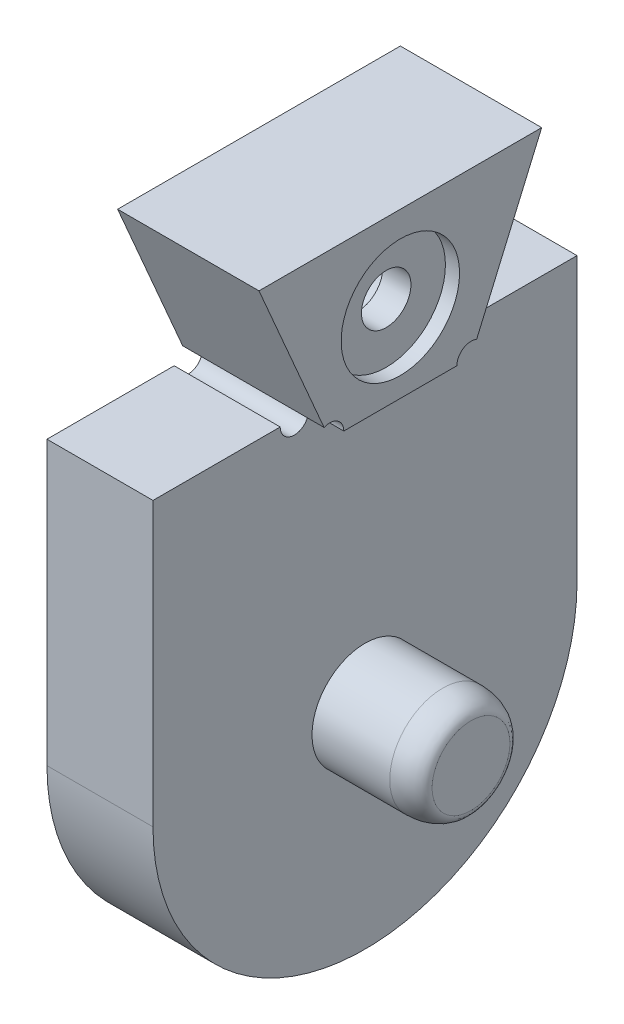
SolidWorks part; units mm, degrees
other "Markup1"
sketch "Sketch42" plane through (-7.99, -35.0001, 20.95) normal (0.6581, -0.0086, 0.7529) x (0.7529, -0.0016, -0.6581)
ref_plane "Front Plane" through (0, 0, 0) normal (0, 0, 1) x (1, 0, 0)
ref_plane "Top Plane" through (0, 0, 0) normal (0, 1, 0) x (1, 0, 0)
ref_plane "Right Plane" through (0, 0, 0) normal (1, 0, 0) x (0, 0, -1)
sketch "Sketch2" plane through (0, 0, 0) normal (0, 0, 1) x (1, 0, 0)
  line L0 (-7.65, 18.1811) -> (-7.65, 14.59)
  line L1 (-7.65, 14.59) -> (7.65, 14.59)
  line L2 (7.65, 14.59) -> (7.65, 18.1811)
  line L3 (7.65, 18.1811) -> (9.45, 18.1811)
  line L4 (9.45, 18.1811) -> (9.45, 21.2003)
  line L5 (-7.65, 18.1811) -> (-9.45, 18.1811)
  line L6 (-9.45, 18.1811) -> (-9.45, 21.2003)
  line L7 (-14.7095, 40) -> (-23, 40)
  line L8 (-23, 40) -> (-23, 0)
  line L10 (14.7095, 40) -> (23, 40)
  line L11 (23, 40) -> (23, 0)
  line L13 (-23, 0) -> (23, 0)
  arc A0 (14.7095, 40) -> (-14.7095, 40) centre (0, 40) ccw
  arc A4 (9.45, 21.2003) -> (-9.45, 21.2003) centre (0, 31.9993) ccw
  point P6 (0, 14.59)
  point P15 (0, 0)
  dimension "D1" = 8.2905
  dimension "D12" = 3.5911
  dimension "D16" = 14.35
  dimension "D17" = 14.7095
  dimension "D2" = 8.2905
  dimension "D3" = 25.41
  dimension "D4" = 40
  dimension "D5" = 0
  dimension "D6" = 0
  dimension "D7" = 46
  dimension "D9" = 3.0191
  dimension "D10" = 1.8
  dimension "D11" = 1.8
  dimension "D13" = 15.3
  dimension "D14" = 3.0191
  dimension "D15" = 3.5911
extrude "Boss-Extrude1" add sketch "Sketch2" along normal blind 20.95
sketch "Sketch3" plane through (0, 0, 0) normal (0, 0, 1) x (1, 0, 0)
  line L7 (-14.7095, 40) -> (-23, 40)
  line L8 (-23, 40) -> (-23, 0)
  line L9 (14.7095, 40) -> (23, 40)
  line L10 (23, 40) -> (23, 0)
  line L11 (-23, 0) -> (23, 0)
  line L12 (23, 40) -> (14.7095, 40) construction
  line L13 (-23, 40) -> (-23, 0) construction
  line L17 (-23, 0) -> (23, 0) construction
  line L19 (23, 0) -> (23, 40) construction
  arc A0 (14.7095, 40) -> (-14.7095, 40) centre (0, 40) ccw
  arc A1 (14.7095, 40) -> (-14.7095, 40) centre (0, 40) ccw construction
  dimension "D1" = 0
extrude "Boss-Extrude2" add sketch "Sketch3" against normal blind 9.05
sketch "Sketch6" plane through (0, 0, 20.95) normal (0, 0, 1) x (1, 0, 0)
  line L0 (-14.7095, 40) -> (-23, 40) construction
  line L1 (-23, 40) -> (-23, 0) construction
  line L2 (23, 40) -> (14.7095, 40) construction
  line L3 (23, 0) -> (23, 40) construction
  circle A0 centre (-17.5, 32) radius 2
  circle A1 centre (17.5, 32) radius 2
  dimension "D1" = 8
  dimension "D2" = 5.5
  dimension "D3" = 4
  dimension "D4" = 8
  dimension "D5" = 5.5
  dimension "D6" = 4
extrude "Cut-Extrude2" cut sketch "Sketch6" against normal blind 10
sketch "Sketch7" plane through (0, 0, 20.95) normal (0, 0, 1) x (1, 0, 0)
  line L0 (-17.5, 32) -> (17.5, 32) construction
  line L3 (-17.5, 35.75) -> (17.5, 35.75)
  line L4 (-17.5, 28.25) -> (17.5, 28.25)
  arc A2 (-17.5, 35.75) -> (-17.5, 28.25) centre (-17.5, 32) ccw
  arc A3 (17.5, 28.25) -> (17.5, 35.75) centre (17.5, 32) ccw
  circle A4 centre (-17.5, 32) radius 2 construction
  circle A5 centre (-17.5, 32) radius 2 construction
  circle A6 centre (17.5, 32) radius 2 construction
  point P2 (0, 32)
  dimension "D2" = 7.5
  dimension "D3" = 1.75
  dimension "D4" = 1.75
  dimension "D1" = 3.75
extrude "Cut-Extrude3" cut sketch "Sketch7" against normal blind 2.75
sketch "Sketch8" plane through (0, 0, 20.95) normal (0, 0, 1) x (1, 0, 0)
  line L0 (-14.7095, 40) -> (-23, 40) construction
  line L1 (-14.7095, 40) -> (-23, 40)
  line L2 (-14.7095, 40) -> (-14.7095, 36.75)
  line L3 (-14.7095, 36.75) -> (-23, 36.75)
  line L4 (-23, 40) -> (-23, 36.75)
  line L5 (14.7095, 40) -> (23, 40)
  line L6 (14.7095, 40) -> (14.7095, 36.75)
  line L7 (14.7095, 36.75) -> (23, 36.75)
  line L8 (23, 40) -> (23, 36.75)
  line L9 (-23, 40) -> (-23, 0) construction
  line L10 (-13.8512, 35.75) -> (-17.5, 35.75) construction
  line L11 (17.5, 35.75) -> (13.8512, 35.75) construction
  line L12 (23, 0) -> (23, 40) construction
  line L13 (23, 40) -> (14.7095, 40) construction
  dimension "D2" = 1
  dimension "D3" = 1
extrude "Cut-Extrude4" cut sketch "Sketch8" along normal through all both and the other way through all
sketch "Sketch11" plane through (0, 0, -9.05) normal (0, 0, -1) x (-1, 0, 0)
  circle A0 centre (0, 40) radius 11.15
  arc A1 (14.7095, 40) -> (-14.7095, 40) centre (0, 40) ccw construction
  dimension "D1" = 22.3
extrude "Bearing Hole" cut sketch "Sketch11" against normal blind 7.3
sketch "Sketch9" plane through (0, 14.59, -19.25) normal (0, 1, 0) x (-1, 0, 0)
  line L0 (7.65, 40.2) -> (-7.65, 40.2) construction
  line L1 (-6.15, 37.7) -> (6.15, 37.7)
  line L2 (-6.15, 37.7) -> (-6.15, 16.2)
  line L3 (-6.15, 16.2) -> (6.15, 16.2)
  line L4 (6.15, 37.7) -> (6.15, 16.2)
  line L8 (-7.65, 40.2) -> (-7.65, 19.25) construction
  line L9 (7.65, 40.2) -> (7.65, 19.25) construction
  line L10 (7.65, 10.2) -> (-7.65, 10.2) construction
  dimension "D1" = 2.5
  dimension "D2" = 1.5
  dimension "D3" = 1.5
  dimension "D4" = 6
extrude "Wire Hole" cut sketch "Sketch9" against normal through all
sketch "Sketch12" plane through (0, 0, 0) normal (0, -1, 0) x (1, 0, 0)
  line L0 (-23, -9.05) -> (23, -9.05) construction
  line L1 (-23, -9.05) -> (23, -9.05)
  line L2 (-23, -9.05) -> (-23, 20.95)
  line L3 (-23, 20.95) -> (23, 20.95)
  line L4 (23, -9.05) -> (23, 20.95)
  line L5 (-23, 20.95) -> (23, 20.95) construction
  line L7 (-23, 20.95) -> (-23, -9.05) construction
  point P4 (0, -9.05)
  dimension "D1" = 0
  dimension "D2" = 0
  dimension "D3" = 0
  dimension "D4" = 0
extrude "Boss-Extrude3" add sketch "Sketch12" along normal blind 0.0001
sketch "Sketch13" plane through (23, 0, 0) normal (1, 0, 0) x (0, 0, -1)
  line L0 (-20.95, -0.0001) -> (-20.95, -20.0001)
  line L1 (9.05, -0.0001) -> (9.05, -20.0001)
  line L6 (9.05, 36.75) -> (-20.95, 36.75)
  line L7 (-20.95, 36.75) -> (-20.95, -0.0001)
  line L8 (-20.95, -0.0001) -> (9.05, -0.0001)
  line L9 (9.05, -0.0001) -> (9.05, 36.75)
  line L12 (-20.95, -0.0001) -> (9.05, -0.0001)
  arc A0 (-20.95, -20.0001) -> (9.05, -20.0001) centre (-5.95, -20.0001) ccw
  dimension "D1" = 0
  dimension "D2" = 20
extrude "Boss-Extrude4" add sketch "Sketch13" against normal blind 7.5
sketch "Sketch14" plane through (-23, 0, 0) normal (-1, 0, 0) x (0, 0, 1)
  line L0 (-9.05, -20.0001) -> (-9.05, -0.0001)
  line L1 (-9.05, -0.0001) -> (20.95, -0.0001)
  line L2 (20.95, -0.0001) -> (20.95, -20.0001)
  arc A0 (-9.05, -20.0001) -> (20.95, -20.0001) centre (5.95, -20.0001) ccw
extrude "Boss-Extrude5" add sketch "Sketch14" against normal blind 7.5
sketch "Sketch21" plane through (23, 0, 0) normal (1, 0, 0) x (0, 0, -1)
  line L0 (-20.95, -20.0001) -> (-20.95, 36.75)
  line L1 (-20.95, 36.75) -> (9.05, 36.75)
  line L2 (9.05, 36.75) -> (9.05, -20.0001)
  arc A0 (-20.95, -20.0001) -> (9.05, -20.0001) centre (-5.95, -20.0001) ccw
extrude "Boss-Extrude9" add sketch "Sketch21" along normal blind 2.5
sketch "Sketch15" plane through (-23, 0, 0) normal (-1, 0, 0) x (0, 0, 1)
  circle A0 centre (5.95, -20.0001) radius 4
extrude "Cut-Extrude5" cut sketch "Sketch15" against normal through all
sketch "Sketch17" plane through (25.5, 0, -23) normal (-1, 0, 0) x (0, 0, 1)
  line L4 (26.7654, -18.5001) -> (31.1346, -18.5001)
  line L5 (26.7654, -21.5001) -> (31.1346, -21.5001)
  arc A10 (26.7654, -18.5001) -> (26.7654, -21.5001) centre (28.95, -20.0001) ccw
  arc A11 (31.1346, -18.5001) -> (31.1346, -21.5001) centre (28.95, -20.0001) cw
  circle A14 centre (28.95, -20.0001) radius 6.1696
  arc A16 (13.95, -20.0001) -> (43.95, -20.0001) centre (28.95, -20.0001) ccw construction
  circle A17 centre (28.95, -20.0001) radius 4 construction
  point P11 (28.95, -35.0001)
  dimension "D1" = 3
  dimension "D2" = 1.5
  dimension "D3" = 2.65
  dimension "D4" = 2.65
extrude "Boss-Extrude6" add sketch "Sketch17" along normal up to surface (10 mm away) up to face at (15.5, -20.0001, 1.95)
sketch "Sketch18" plane through (-23, 0, 0) normal (-1, 0, 0) x (0, 0, 1)
  circle A0 centre (5.95, -20.0001) radius 4
  dimension "D1" = 8
extrude "Knub" add sketch "Sketch18" against normal offset from surface (15 mm away) 7.5 up to face at (-15.5, -24.0001, 5.95) offset beyond the face yes
sketch "Sketch19" plane through (15.5, 0, 0) normal (-1, 0, 0) x (0, 0, 1)
  circle A0 centre (5.95, -20.0001) radius 4.675
  dimension "D1" = 9.35
extrude "Cut-Extrude6" cut sketch "Sketch19" against normal blind 2
sketch "Sketch24" plane through (0, 0, -1.75) normal (0, 0, -1) x (-1, 0, 0)
  circle A0 centre (0, 40) radius 4.5
  dimension "D1" = 9
extrude "Cut-Extrude7" cut sketch "Sketch24" against normal through all
fillet "Fillet1" radius 0.5 1 edges at (-11.15, 40, -9.05)
sketch "Sketch25" plane through (25.5, 0, 0) normal (1, 0, 0) x (0, 0, -1)
  line L1 (-10.6075, -17.9723) -> (-1.7642, -17.9723)
  line L2 (-10.6075, -17.9723) -> (-10.6075, -22.8066)
  line L3 (-10.6075, -22.8066) -> (-1.7642, -22.8066)
  line L4 (-1.7642, -17.9723) -> (-1.7642, -22.8066)
extrude "Boss-Extrude10" add sketch "Sketch25" against normal blind 2
sketch "Sketch27" plane through (0, 14.59, 0) normal (0, 1, 0) x (1, 0, 0)
  line L1 (-6.15, -18.45) -> (6.15, -18.45)
  line L2 (-6.15, -18.45) -> (-6.15, 3.05)
  line L3 (-6.15, 3.05) -> (6.15, 3.05)
  line L4 (6.15, -18.45) -> (6.15, 3.05)
extrude "Cut-Extrude8" cut sketch "Sketch27" against normal through all
sketch "Sketch28" plane through (0, -0.0001, 0) normal (0, -1, 0) x (1, 0, 0)
  line L1 (-6.15, -3.05) -> (-6.15, 18.45) construction
  line L2 (6.15, 18.45) -> (6.15, -3.05) construction
  line L4 (-6.15, 7.7) -> (0, 17.95)
  line L5 (0, 17.95) -> (6.15, 7.7)
  line L8 (-6.15, -3.05) -> (6.15, -3.05)
  line L9 (-6.15, 18.45) -> (-6.15, -3.05)
  line L10 (6.15, 18.45) -> (-6.15, 18.45)
  line L11 (6.15, -3.05) -> (6.15, 18.45)
  line L13 (-6.15, 18.45) -> (-6.15, 7.7)
  line L14 (6.15, 18.45) -> (-6.15, 18.45)
  line L15 (6.15, 7.7) -> (6.15, 18.45)
  dimension "D1" = 0
  dimension "D2" = 0.5
extrude "Boss-Extrude11" add sketch "Sketch28" against normal up to surface (14.5901 mm away) up to face at (0, 14.59, 9.85)
sketch "Sketch29" plane through (0, 0, 20.95) normal (0, 0, 1) x (1, 0, 0)
  line L1 (-7.65, 14.59) -> (7.55, 14.59)
  line L2 (-7.65, 14.59) -> (-7.65, 11.59)
  line L3 (-7.65, 11.59) -> (7.55, 11.59)
  line L4 (7.55, 14.59) -> (7.55, 11.59)
  dimension "D1" = 3
extrude "Cut-Extrude9" cut sketch "Sketch29" against normal up to surface (20.95 mm away) up to face at (4.5, 40, 0)
sketch "Sketch30" plane through (-23, 0, 0) normal (-1, 0, 0) x (0, 0, 1)
  line L9 (-9.05, 54.7095) -> (20.95, 54.7095)
  line L10 (-9.05, 54.7095) -> (-9.05, 11.59)
  line L11 (-9.05, 11.59) -> (20.95, 11.59)
  line L12 (20.95, 54.7095) -> (20.95, 11.59)
extrude "Cut-Extrude10" cut sketch "Sketch30" against normal through all
sketch "Sketch31" plane through (-23, 0, 0) normal (-1, 0, 0) x (0, 0, 1)
  line L0 (-4.05, 11.59) -> (15.95, 11.59)
  line L1 (-9.05, 11.59) -> (20.95, 11.59) construction
  line L2 (15.95, 11.59) -> (10.95, -0.0001)
  line L3 (20.95, -0.0001) -> (-9.05, -0.0001) construction
  line L4 (10.95, -0.0001) -> (20.95, -0.0001)
  line L5 (20.95, -0.0001) -> (20.95, -20.0001)
  line L6 (-4.05, 11.59) -> (0.95, -0.0001)
  line L7 (0.95, -0.0001) -> (-9.05, -0.0001)
  line L8 (-9.05, -0.0001) -> (-9.05, -20.0001)
  line L10 (-16.4236, 17.1968) -> (27.953, 17.1968)
  line L11 (-16.4236, 17.1968) -> (-16.4236, -37.278)
  line L12 (-16.4236, -37.278) -> (27.953, -37.278)
  line L13 (27.953, 17.1968) -> (27.953, -37.278)
  arc A0 (-9.05, -20.0001) -> (20.95, -20.0001) centre (5.95, -20.0001) ccw construction
  arc A1 (-9.05, -20.0001) -> (20.95, -20.0001) centre (5.95, -20.0001) ccw
  point P19 (5.95, -0.0001)
  point P20 (5.95, 11.59)
  dimension "D1" = 10
  dimension "D2" = 5
  dimension "D3" = 20
  dimension "D4" = 0
extrude "Cut-Extrude12" cut sketch "Sketch31" against normal through all
sketch "Sketch32" plane through (0, 11.59, 0) normal (0, 1, 0) x (1, 0, 0)
  line L1 (25.5, 9.05) -> (-13, 9.05)
  line L2 (25.5, 9.05) -> (25.5, -20.95)
  line L3 (25.5, -20.95) -> (-13, -20.95)
  line L4 (-13, 9.05) -> (-13, -20.95)
  line L5 (-23, -0.95) -> (-23, 9.05) construction
  dimension "D1" = 10
extrude "Cut-Extrude13" cut sketch "Sketch32" against normal blind 26
sketch "Sketch39" plane through (0, -14.41, 0) normal (0, 1, 0) x (1, 0, 0)
  line L1 (12.9636, 12.484) -> (32.0996, 12.484)
  line L2 (12.9636, 12.484) -> (12.9636, -26.7922)
  line L3 (12.9636, -26.7922) -> (32.0996, -26.7922)
  line L4 (32.0996, 12.484) -> (32.0996, -26.7922)
extrude "Cut-Extrude18" cut sketch "Sketch39" against normal through all
sketch "Sketch33" plane through (-23, 0, 0) normal (-1, 0, 0) x (0, 0, 1)
  line L0 (-4.05, 11.59) -> (15.95, 11.59) construction
  circle A0 centre (5.95, 5.59) radius 2.75
  point P5 (5.95, 11.59)
  dimension "D1" = 6
  dimension "D2" = 5.5
extrude "Cut-Extrude14" cut sketch "Sketch33" against normal offset from surface (7 mm away) 3 up to face at (-13, 5.795, 5.95)
sketch "Sketch34" plane through (-16, 0, 0) normal (-1, 0, 0) x (0, 0, 1)
  circle A0 centre (5.95, 5.59) radius 1.75
  dimension "D1" = 3.5
extrude "Cut-Extrude15" cut sketch "Sketch34" against normal blind 10
sketch "Sketch37" plane through (-13, 0, 0) normal (1, 0, 0) x (0, 0, -1)
  circle A0 centre (-5.95, 5.59) radius 4.1887
extrude "Cut-Extrude17" cut sketch "Sketch37" against normal offset from surface (1 mm away) 2 up to face at (-16, 3.84, 5.95)
sketch "Sketch40" plane through (-8, 0, 0) normal (1, 0, 0) x (0, 0, -1)
  circle A0 centre (-5.95, -20.0001) radius 4
  circle A1 centre (-5.95, -20.0001) radius 3.75
  circle A2 centre (-5.95, -20.0001) radius 4 construction
  dimension "D1" = 0
extrude "Cut-Extrude19" cut sketch "Sketch40" against normal up to surface (7.5 mm away) up to face at (-15.5, -24.0001, 5.95)
fillet "Fillet4" radius 2 1 edges at (-8, -16.2501, 5.95) second distance 1 first distance on face at (-8, -16.2501, 5.95)
sketch "Sketch41" plane through (-23, 0, 0) normal (-1, 0, 0) x (0, 0, 1)
  line L0 (-4.05, 11.59) -> (0.95, -0.0001) construction
  line L1 (0.95, -0.0001) -> (-9.05, -0.0001) construction
  line L2 (20.95, -0.0001) -> (10.95, -0.0001) construction
  line L3 (10.95, -0.0001) -> (15.95, 11.59) construction
  line L4 (0.5539, 0.9181) -> (0.95, -0.0001)
  line L5 (0.95, -0.0001) -> (-0.05, -0.0001)
  line L6 (11.3461, 0.9181) -> (10.95, -0.0001)
  line L7 (10.95, -0.0001) -> (11.95, -0.0001)
  arc A0 (0.5539, 0.9181) -> (-0.05, -0.0001) centre (0.95, -0.0001) cw
  arc A1 (11.95, -0.0001) -> (11.3461, 0.9181) centre (10.95, -0.0001) cw
  dimension "D1" = 1
extrude "Cut-Extrude20" cut sketch "Sketch41" against normal through all
